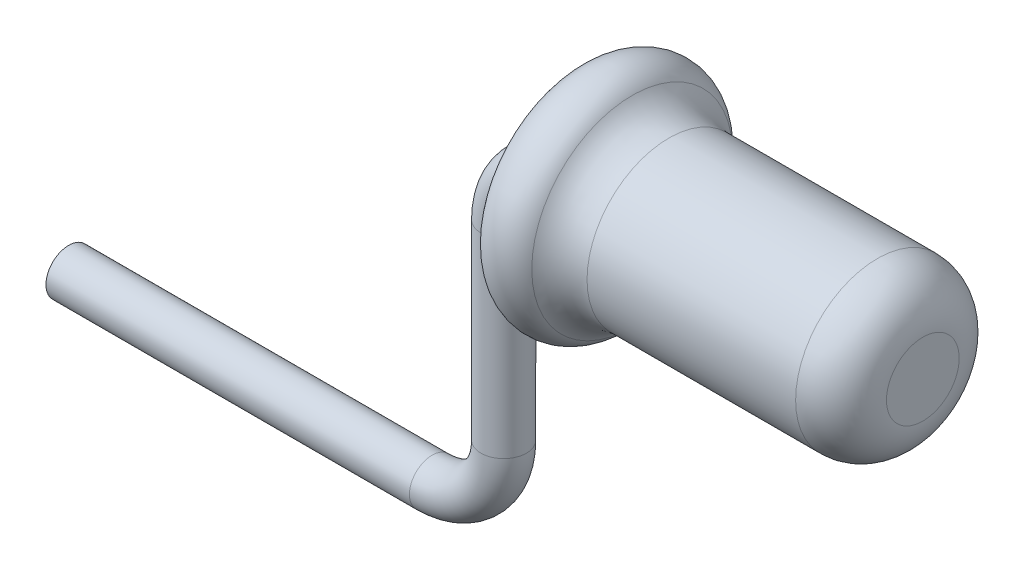
SolidWorks part; units mm, degrees
ref_plane "Front" through (0, 0, 0) normal (0, 0, 1) x (1, 0, 0)
ref_plane "Top" through (0, 0, 0) normal (0, 1, 0) x (1, 0, 0)
ref_plane "Right" through (0, 0, 0) normal (1, 0, 0) x (0, 0, -1)
sketch "Sketch1" plane through (0, 0, 0) normal (0, 0, 1) x (1, 0, 0)
  line L0 (-15.5632, 0) -> (24.4368, 0)
  line L1 (55, 0) -> (-55, 0) construction
  line L2 (32.3103, 7.8735) -> (32.3103, 28.8735)
  line L3 (40.1838, 36.747) -> (75.1838, 36.747)
  arc A0 (24.4368, 0) -> (32.3103, 7.8735) centre (24.4368, 7.8735) ccw
  arc A1 (40.1838, 36.747) -> (32.3103, 28.8735) centre (40.1838, 28.8735) ccw
  point P6 (0, 0)
  point P8 (24.4368, 0)
  point P12 (32.3103, 28.8735)
  dimension "D3" = 15.747
  dimension "D4" = 15.747
  dimension "D1" = 40
  dimension "D2" = 35
  dimension "D5" = 21
ref_plane "Plane1" through (-15.5632, 0, 0) normal (1, 0, 0) x (0, 0, -1)
sketch "Sketch3" plane through (-15.5632, 0, 0) normal (1, 0, 0) x (0, 0, -1)
  circle A0 centre (0, 0) radius 2.5
  point P0 (0, 0)
sweep "Sweep1" add profiles "Sketch3" path "Sketch1"
sketch "Sketch4" plane through (0, 0, 0) normal (0, 0, 1) x (1, 0, 0)
  line L1 (75.1838, 39.247) -> (40.1838, 39.247) construction
  line L3 (75.1838, 39.247) -> (40.1838, 39.247)
  line L4 (40.1838, 39.247) -> (40.1838, 45.747)
  line L5 (50.4866, 45.747) -> (73.4428, 45.747)
  line L6 (78.4428, 40.747) -> (78.4428, 39.247)
  line L7 (75.1838, 39.247) -> (40.1838, 39.247)
  line L8 (75.1838, 39.247) -> (75.1838, 36.747)
  line L10 (75.1838, 34.247) -> (75.1838, 39.247) construction
  line L12 (75.1838, 36.747) -> (78.4428, 36.747)
  line L14 (78.4428, 36.747) -> (78.4428, 39.247)
  line L16 (40.1838, 36.747) -> (78.4428, 36.747) construction
  line L17 (40.1838, 39.247) -> (40.1838, 34.247) construction
  arc A0 (46.4512, 47.7948) -> (40.1838, 45.747) centre (43.652, 45.747) ccw
  arc A2 (78.4428, 40.747) -> (73.4428, 45.747) centre (73.4428, 40.747) ccw
  arc A3 (50.4866, 45.747) -> (46.4512, 47.7948) centre (50.4866, 50.747) cw
  point P15 (47.1203, 45.747)
  dimension "D2" = 5
  dimension "D3" = 5
  dimension "D1" = 6.5
revolve "Revolve1" add sketch "Sketch4" angle 360 about L16 region at (58.3286, 42.6694, 0)
